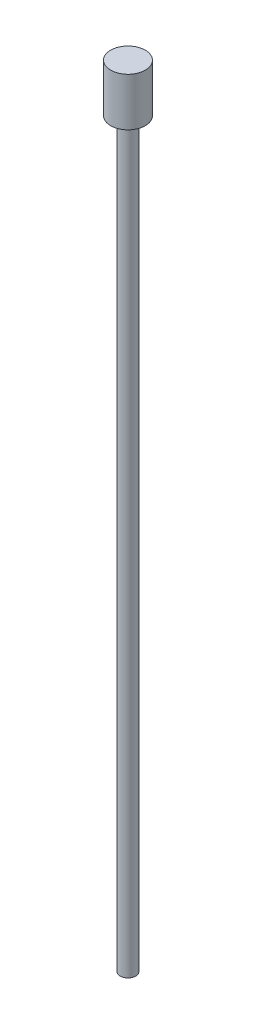
SolidWorks part; units mm, degrees
ref_plane "Plan de face" through (0, 0, 0) normal (0, 0, 1) x (1, 0, 0)
ref_plane "Plan de dessus" through (0, 0, 0) normal (0, 1, 0) x (1, 0, 0)
ref_plane "Plan de droite" through (0, 0, 0) normal (1, 0, 0) x (0, 0, -1)
sketch "Esquisse1" plane through (0, 0, 0) normal (0, 1, 0) x (1, 0, 0)
  circle A0 centre (0, 0) radius 4
  dimension "D1" = 8
extrude "Boss.-Extru.1" add sketch "Esquisse1" along normal blind 385
sketch "Esquisse2" plane through (0, 385, 0) normal (0, 1, 0) x (1, 0, 0)
  circle A0 centre (0, 0) radius 9
  dimension "D1" = 18
extrude "Boss.-Extru.2" add sketch "Esquisse2" along normal blind 25
